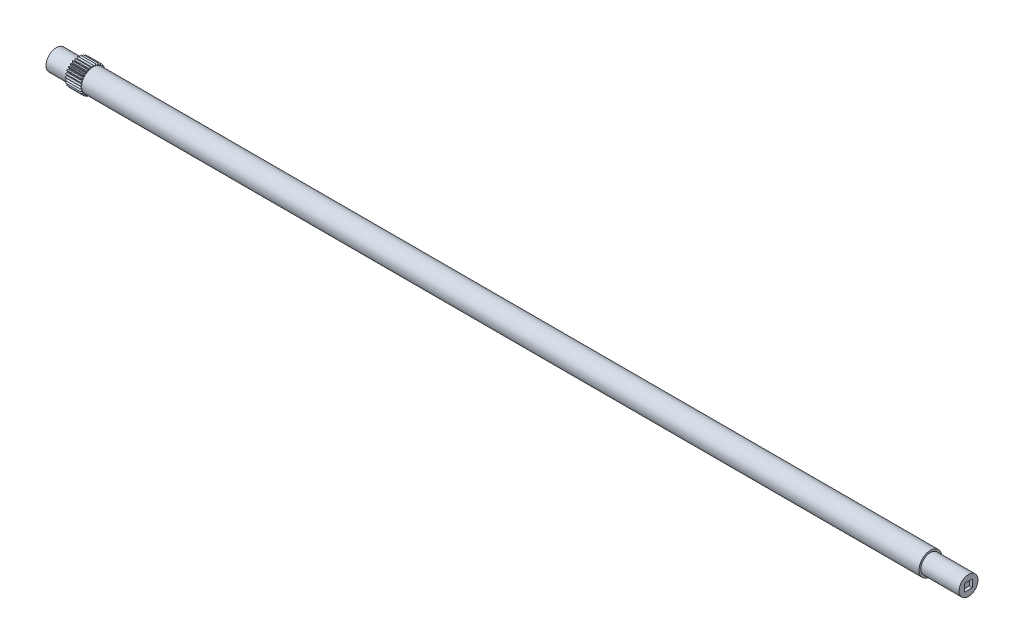
SolidWorks part; units mm, degrees
ref_plane "Front Plane" through (0, 0, 0) normal (0, 0, 1) x (1, 0, 0)
ref_plane "Top Plane" through (0, 0, 0) normal (0, 1, 0) x (1, 0, 0)
ref_plane "Right Plane" through (0, 0, 0) normal (1, 0, 0) x (0, 0, -1)
sketch "Sketch1" plane through (0, 0, 0) normal (0, 0, 1) x (1, 0, 0)
  line L0 (-389.8125, 0) -> (391.911, 0) construction
  line L1 (-371.475, 0) -> (371.475, 0)
  line L2 (-371.475, 0) -> (-371.475, 9.525)
  line L3 (-371.475, 9.525) -> (339.725, 9.525)
  line L4 (339.725, 7.9375) -> (339.725, 9.525)
  line L8 (339.725, 7.9375) -> (371.475, 7.9375)
  line L9 (371.475, 0) -> (371.475, 7.9375)
  dimension "D1" = 711.2
  dimension "D2" = 19.05
  dimension "D3" = 31.75
  dimension "D4" = 15.875
revolve "Revolve1" add sketch "Sketch1" angle 360 about L0
sketch "Sketch2" plane through (-371.475, 0, 0) normal (-1, 0, 0) x (0, 0, 1)
  line L0 (0, 10.795) -> (-0.6789, 9.5008)
  line L1 (0, 10.795) -> (0.6789, 9.5008)
  line L2 (0, 10.795) -> (0, 0) construction
  arc A0 (0.6789, 9.5008) -> (-0.6789, 9.5008) centre (0, 0) ccw
  circle A1 centre (0, 0) radius 9.525 construction
  point P1 (0, 9.525)
  dimension "D1" = 1.27
extrude "Boss-Extrude1" add sketch "Sketch2" against normal blind 12.7
pattern_circular "CirPattern1" count 30 over 360 about axis through (-371.475, 0, 0) along (-1, 0, 0) of "Boss-Extrude1"
sketch "Sketch3" plane through (-371.475, 0, 0) normal (-1, 0, 0) x (0, 0, 1)
  circle A0 centre (0.4942, 0) radius 8.6181
extrude "Boss-Extrude2" add sketch "Sketch3" along normal blind 17.4625
ref_axis "Axis1" through (339.725, 0, 0) along (-1, 0, 0)
sketch "Sketch4" plane through (371.475, 0, 0) normal (1, 0, 0) x (0, 0, -1)
  line L1 (-3.175, -3.175) -> (3.175, -3.175)
  line L2 (-3.175, -3.175) -> (-3.175, 3.175)
  line L3 (-3.175, 3.175) -> (3.175, 3.175)
  line L4 (3.175, -3.175) -> (3.175, 3.175)
  line L5 (-3.175, -3.175) -> (3.175, 3.175) construction
  line L6 (-3.175, 3.175) -> (3.175, -3.175) construction
  point P0 (0, 0)
  dimension "D1" = 6.35
extrude "Magic Box" cut sketch "Sketch4" against normal blind 2.54
